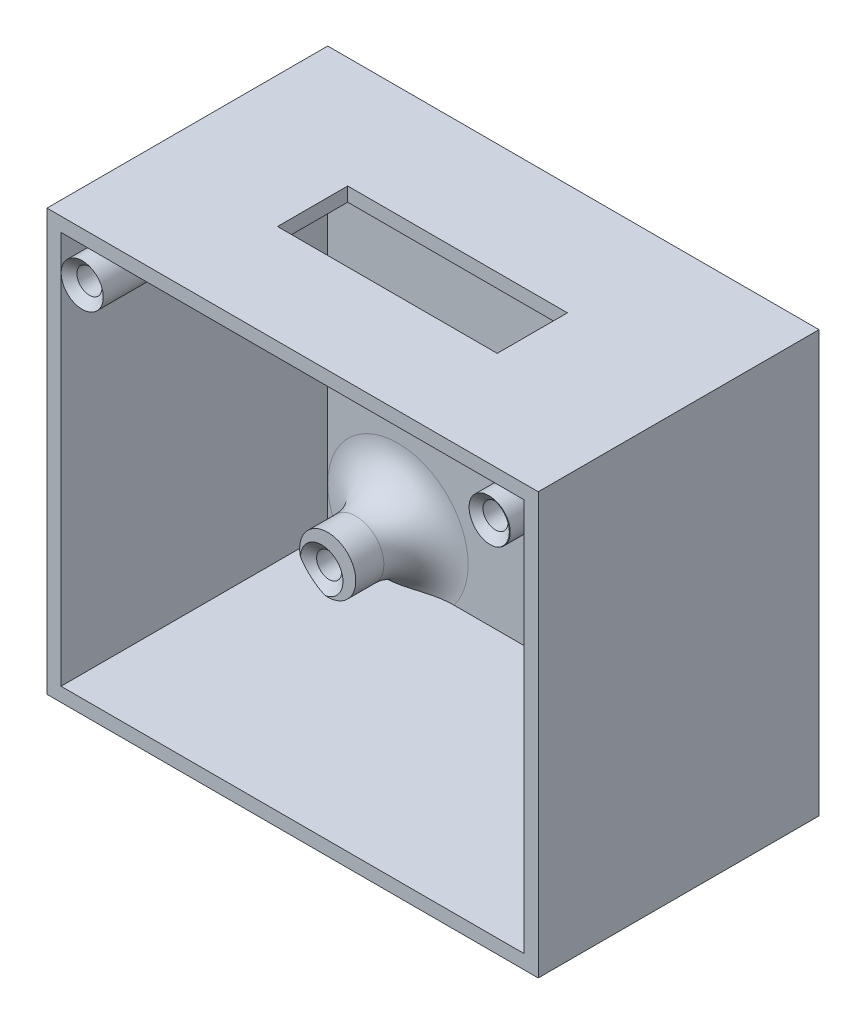
SolidWorks part; units mm, degrees
ref_plane "Front Plane" through (0, 0, 0) normal (0, 0, 1) x (1, 0, 0)
ref_plane "Top Plane" through (0, 0, 0) normal (0, 1, 0) x (1, 0, 0)
ref_plane "Right Plane" through (0, 0, 0) normal (1, 0, 0) x (0, 0, -1)
sketch "Sketch1" plane through (0, 0, 0) normal (0, 0, 1) x (1, 0, 0)
  line L1 (0, 0) -> (35, 0)
  line L2 (0, 0) -> (0, 30)
  line L3 (0, 30) -> (35, 30)
  line L4 (35, 0) -> (35, 30)
  dimension "D1" = 35
  dimension "D2" = 30
extrude "Boss-Extrude1" add sketch "Sketch1" along normal blind 20
shell "Shell1" thickness 1 removed face at (17.5, 15, 20)
sketch "Sketch6" plane through (0, 0, 1) normal (0, 0, 1) x (1, 0, 0)
  line L1 (1, 1) -> (34, 1) construction
  line L2 (1, 29) -> (1, 1) construction
  circle A2 centre (31, 4) radius 2
  circle A3 centre (6, 4) radius 2
  dimension "D1" = 3
  dimension "D2" = 3
  dimension "D3" = 4
  dimension "D4" = 5
  dimension "4" = 4
  dimension "D5" = 25
extrude "Boss-Extrude5" add sketch "Sketch6" along normal blind 5
hole_wizard "CSK for #0 Flat Head Machine Screw (100)1" positions "Sketch7" profile "Sketch8" countersink size "#0" standard "ANSI Inch" end condition through all
sketch "Sketch7" plane through (0, 0, 6) normal (0, 0, 1) x (1, 0, 0)
  point P0 (5.5744, 3.5015)
  point P5 (31, 4)
sketch "Sketch8" plane through (5.5744, 3.5015, 6) normal (1, 0, 0) x (0, -1, 0)
  line L0 (0, 0) -> (0, 6)
  line L1 (0, 6) -> (0.889, 6)
  line L2 (0.889, 6) -> (0.889, 0.5222)
  line L3 (0.889, 0.5222) -> (1.5113, 0)
  line L5 (1.5113, 0) -> (0, 0)
  line L6 (-0.889, 0.5222) -> (-1.5113, 0) construction
  line L11 (0, -6.35) -> (0, 107.95) construction
  dimension "Thru Hole Dia." = 1.778
  dimension "Thru Hole Depth" = 6
  dimension "Near C'Sink Dia." = 3.0226
  dimension "Near C'Sink Angle" = 100
sketch "Sketch11" plane through (0, 0, 1) normal (0, 0, 1) x (1, 0, 0)
  line L0 (35, 30) -> (0, 30) construction
  line L1 (0, 30) -> (0, 0) construction
  line L2 (35, 0) -> (35, 30) construction
  circle A0 centre (3, 27) radius 1.5
  circle A1 centre (32, 27) radius 1.5
  dimension "D1" = 3
  dimension "D2" = 3
  dimension "D3" = 3
  dimension "D4" = 3
  dimension "D5" = 3
  dimension "D6" = 3
extrude "Boss-Extrude6" add sketch "Sketch11" along normal blind 19.5
hole_wizard "CSK for #0 Flat Head Machine Screw (100)2" positions "Sketch14" profile "Sketch15" countersink size "#0" standard "ANSI Inch" end condition through all
sketch "Sketch14" plane through (0, 0, 20.5) normal (0, 0, 1) x (1, 0, 0)
  point P0 (31.9255, 26.9819)
  point P2 (3, 27)
sketch "Sketch15" plane through (31.9255, 26.9819, 20.5) normal (1, 0, 0) x (0, -1, 0)
  line L0 (0, 0) -> (0, 20.5)
  line L1 (0, 20.5) -> (0.889, 20.5)
  line L2 (0.889, 20.5) -> (0.889, 0.5222)
  line L3 (0.889, 0.5222) -> (1.5113, 0)
  line L5 (1.5113, 0) -> (0, 0)
  line L6 (-0.889, 0.5222) -> (-1.5113, 0) construction
  line L11 (0, -6.35) -> (0, 107.95) construction
  dimension "Thru Hole Dia." = 1.778
  dimension "Thru Hole Depth" = 20.5
  dimension "Near C'Sink Dia." = 3.0226
  dimension "Near C'Sink Angle" = 100
sketch "Sketch16" plane through (0, 30, 0) normal (0, 1, 0) x (1, 0, 0)
  line L0 (35, -20) -> (35, 0) construction
  line L1 (25, -12.9241) -> (9.3479, -12.9241)
  line L2 (25, -12.9241) -> (25, -7.9241)
  line L3 (25, -7.9241) -> (9.3479, -7.9241)
  line L4 (9.3479, -12.9241) -> (9.3479, -7.9241)
  dimension "D1" = 10
  dimension "D2" = 5
extrude "Cut-Extrude1" cut sketch "Sketch16" against normal blind 7.5
fillet "Fillet1" radius 3 2 edges at (30.5, 27, 1) (1.5, 27, 1)
fillet "Fillet2" radius 3 2 edges at (29, 4, 1) (4, 4, 1)
